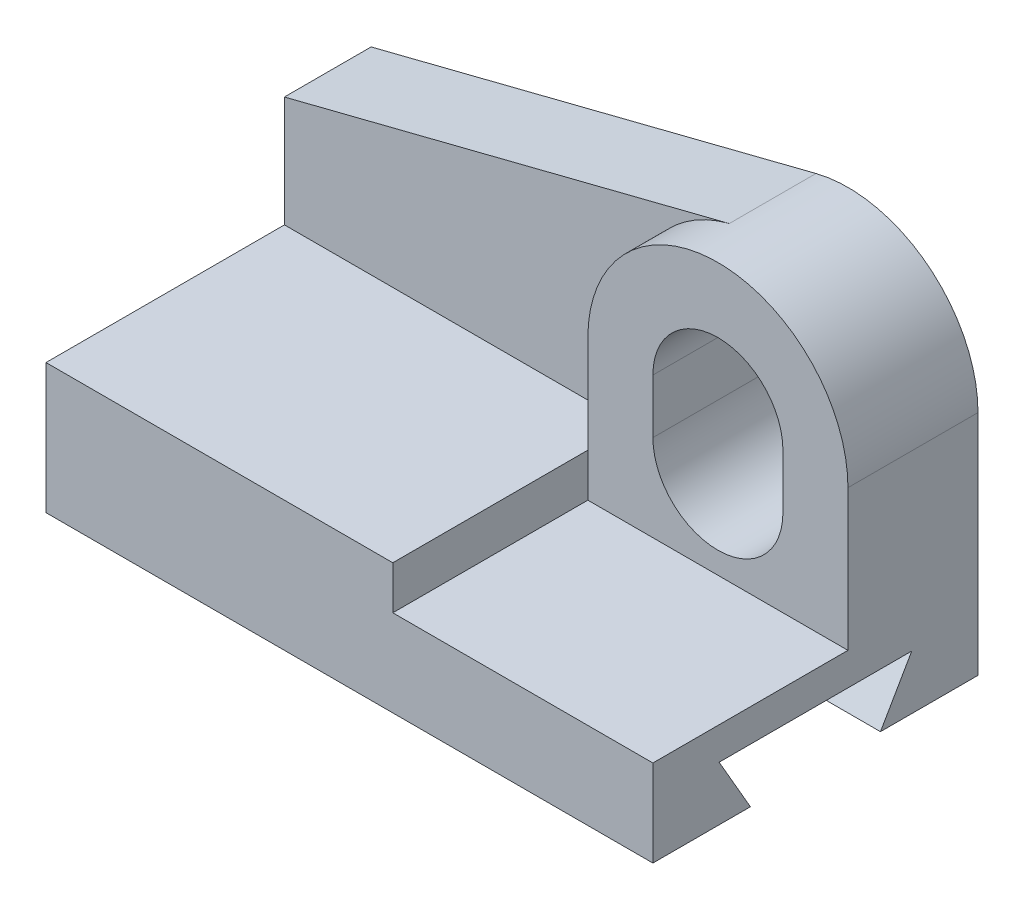
SolidWorks part; units mm, degrees
ref_plane "前视基准面" through (0, 0, 0) normal (0, 0, 1) x (1, 0, 0)
ref_plane "上视基准面" through (0, 0, 0) normal (0, 1, 0) x (1, 0, 0)
ref_plane "右视基准面" through (0, 0, 0) normal (1, 0, 0) x (0, 0, -1)
other "Configuration Table"
sketch "草图1" plane through (0, 0, 0) normal (0, 1, 0) x (1, 0, 0)
  line L5 (-28, -15) -> (28, -15)
  line L6 (-28, -15) -> (-28, 15)
  line L11 (-28, 15) -> (28, 15)
  line L12 (28, -15) -> (28, 15)
  line L13 (-28, -15) -> (28, 15) construction
  line L14 (-28, 15) -> (28, -15) construction
  point P0 (0, 0)
  dimension "D1" = 56
  dimension "D2" = 30
extrude "凸台-拉伸1" add sketch "草图1" along normal blind 8
sketch "草图2" plane through (0, 8, 0) normal (0, 1, 0) x (1, 0, 0)
  line L4 (28, -15) -> (28, 15)
  line L5 (28, 15) -> (-28, 15)
  line L6 (-28, 15) -> (-28, -15)
  line L7 (-28, -15) -> (28, -15)
  line L8 (28, -15) -> (28, 15)
  line L9 (28, 15) -> (-28, 15)
  line L10 (-28, 15) -> (-28, -15)
  line L11 (-28, -15) -> (28, -15)
  dimension "D1" = 0
sketch "草图3" plane through (0, 8, 0) normal (0, 1, 0) x (1, 0, 0)
  line L0 (-28, -15) -> (4, -15)
  line L1 (-28, -15) -> (-28, 15)
  line L2 (-28, 15) -> (4, 15)
  line L3 (4, 15) -> (4, -15)
  dimension "D1" = 32
extrude "凸台-拉伸2" add sketch "草图3" along normal blind 4
ref_plane "基准面1" through (0, 0, -15) normal (0, 0, 1) x (1, 0, 0)
sketch "草图7" plane through (0, 0, -15) normal (0, 0, 1) x (1, 0, 0)
  line L0 (-28, 12) -> (-28, 22.2209)
  line L1 (-28, 22.2209) -> (13.05, 32.6318)
  line L2 (4, 8) -> (4, 21)
  line L3 (28, 8) -> (28, 21)
  line L4 (4, 8) -> (28, 8)
  line L5 (28, 21) -> (28, 8)
  line L6 (16, 21) -> (16, 16) construction
  line L7 (22, 21) -> (22, 16)
  line L8 (10, 21) -> (10, 16)
  line L9 (-28, 12) -> (4, 12)
  line L10 (4, 12) -> (4, 21)
  arc A0 (28, 21) -> (4, 21) centre (16, 21) ccw
  arc A1 (22, 21) -> (10, 21) centre (16, 21) ccw
  arc A2 (10, 16) -> (22, 16) centre (16, 16) ccw
  point P2 (16, 18.5)
  dimension "D1" = 12
  dimension "D4" = 6
  dimension "D2" = 8
  dimension "D3" = 5
extrude "凸台-拉伸3" add sketch "草图7" along normal blind 12 contours L3 A0 L2 L4 A2 L8 A1 L7 region at (4.3466, 16.5, -15)
extrude "凸台-拉伸4" add sketch "草图7<4>" along normal blind 8 contours A0 L1 L0 L9 L2 region at (-9.9005, 19.6683, -15)
sketch "草图7<4>" plane through (0, 0, -15) normal (0, 0, 1) x (1, 0, 0) same geometry as "草图7"
sketch "草图13" plane through (0, 0, 0) normal (1, 0, 0) x (0, 0, -1)
  line L0 (0, 0) -> (-6, 0)
  line L1 (-15, 0) -> (15, 0) construction
  line L2 (0, 0) -> (6, 0)
  line L3 (-8.8868, 5) -> (8.8868, 5)
  line L4 (-6, 0) -> (-8.8868, 5)
  line L5 (6, 0) -> (8.8868, 5)
  line L12 (-15, 0) -> (15, 0)
  line L13 (15, 0) -> (15, 21)
  line L14 (15, 21) -> (3, 21)
  line L15 (3, 21) -> (3, 8)
  line L16 (3, 8) -> (-15, 8)
  line L17 (-15, 8) -> (-15, 0)
  line L18 (-15, 0) -> (15, 0)
  line L19 (15, 0) -> (15, 21)
  line L20 (15, 21) -> (3, 21)
  line L21 (3, 21) -> (3, 8)
  line L22 (3, 8) -> (-15, 8)
  line L23 (-15, 8) -> (-15, 0)
  dimension "D1" = 6
  dimension "D3" = 60
  dimension "D4" = 60
  dimension "D5" = 5
  dimension "D2" = 0
extrude "切除-拉伸1" cut sketch "草图13" against normal through all both and the other way through all contours L2 L5 L3 L4 L0 region at (0, 2.6616, 0)
